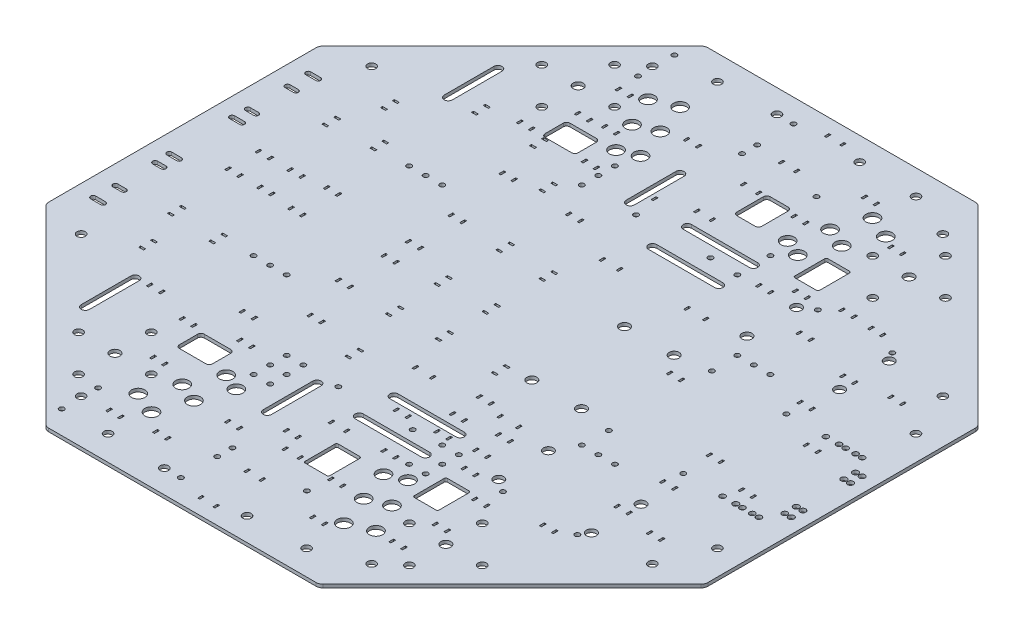
SolidWorks part; units mm, degrees
ref_plane "前视基准面" through (0, 0, 0) normal (0, 0, 1) x (1, 0, 0)
ref_plane "上视基准面" through (0, 0, 0) normal (0, 1, 0) x (1, 0, 0)
ref_plane "右视基准面" through (0, 0, 0) normal (1, 0, 0) x (0, 0, -1)
other "Configuration Table"
ref_plane "基准面1" through (0, 0, 0) normal (0, -1, 0) x (1, 0, 0)
sketch "草图1" plane through (0, 0, 0) normal (0, -1, 0) x (1, 0, 0)
  line L0 (-199.1726, 80.8431) -> (-199.1726, -80.8431)
  line L1 (-198.001, -83.6716) -> (-83.6716, -198.001)
  line L2 (-80.8431, -199.1726) -> (80.8431, -199.1726)
  line L3 (83.6716, -198.001) -> (198.001, -83.6716)
  line L4 (199.1726, -80.8431) -> (199.1726, 80.8431)
  line L5 (198.001, 83.6716) -> (83.6716, 198.001)
  line L6 (80.8431, 199.1726) -> (-80.8431, 199.1726)
  line L7 (-83.6716, 198.001) -> (-198.001, 83.6716)
  line L8 (-182.1726, 63.5) -> (-188.1726, 63.5)
  line L9 (-188.1726, 66.5) -> (-182.1726, 66.5)
  line L10 (-182.1726, 17.5) -> (-188.1726, 17.5)
  line L11 (-188.1726, 20.5) -> (-182.1726, 20.5)
  line L12 (-182.1726, -66.5) -> (-188.1726, -66.5)
  line L13 (-188.1726, -63.5) -> (-182.1726, -63.5)
  line L14 (-182.1726, -20.5) -> (-188.1726, -20.5)
  line L15 (-188.1726, -17.5) -> (-182.1726, -17.5)
  line L16 (-182.6726, 50.5) -> (-187.6726, 50.5)
  line L17 (-187.6726, 53.5) -> (-182.6726, 53.5)
  line L18 (-182.6726, 26.5) -> (-187.6726, 26.5)
  line L19 (-187.6726, 29.5) -> (-182.6726, 29.5)
  line L20 (-182.6726, -53.5) -> (-187.6726, -53.5)
  line L21 (-187.6726, -50.5) -> (-182.6726, -50.5)
  line L22 (-182.6726, -29.5) -> (-187.6726, -29.5)
  line L23 (-187.6726, -26.5) -> (-182.6726, -26.5)
  line L24 (61.2, 58) -> (61.2, 55)
  line L25 (61.2, 55) -> (60, 55)
  line L26 (60, 55) -> (60, 58)
  line L27 (60, 58) -> (61.2, 58)
  line L28 (50, 58) -> (50, 55)
  line L29 (50, 55) -> (48.8, 55)
  line L30 (48.8, 55) -> (48.8, 58)
  line L31 (48.8, 58) -> (50, 58)
  line L32 (-1.2, 58) -> (-1.2, 55)
  line L33 (-1.2, 55) -> (-2.4, 55)
  line L34 (-2.4, 55) -> (-2.4, 58)
  line L35 (-2.4, 58) -> (-1.2, 58)
  line L36 (9.2, 58) -> (9.2, 55)
  line L37 (9.2, 55) -> (8, 55)
  line L38 (8, 55) -> (8, 58)
  line L39 (8, 58) -> (9.2, 58)
  line L40 (61.2, -58) -> (60, -58)
  line L41 (60, -58) -> (60, -55)
  line L42 (60, -55) -> (61.2, -55)
  line L43 (61.2, -55) -> (61.2, -58)
  line L44 (50, -58) -> (48.8, -58)
  line L45 (48.8, -58) -> (48.8, -55)
  line L46 (48.8, -55) -> (50, -55)
  line L47 (50, -55) -> (50, -58)
  line L48 (-1.2, -58) -> (-2.4, -58)
  line L49 (-2.4, -58) -> (-2.4, -55)
  line L50 (-2.4, -55) -> (-1.2, -55)
  line L51 (-1.2, -55) -> (-1.2, -58)
  line L52 (9.2, -58) -> (8, -58)
  line L53 (8, -58) -> (8, -55)
  line L54 (8, -55) -> (9.2, -55)
  line L55 (9.2, -55) -> (9.2, -58)
  line L56 (10, -160) -> (11.2, -160)
  line L57 (11.2, -160) -> (11.2, -163)
  line L58 (11.2, -163) -> (10, -163)
  line L59 (10, -163) -> (10, -160)
  line L60 (0.8, -160) -> (2, -160)
  line L61 (2, -160) -> (2, -163)
  line L62 (2, -163) -> (0.8, -163)
  line L63 (0.8, -163) -> (0.8, -160)
  line L64 (10, -137) -> (11.2, -137)
  line L65 (11.2, -137) -> (11.2, -140)
  line L66 (11.2, -140) -> (10, -140)
  line L67 (10, -140) -> (10, -137)
  line L68 (0.8, -137) -> (2, -137)
  line L69 (2, -137) -> (2, -140)
  line L70 (2, -140) -> (0.8, -140)
  line L71 (0.8, -140) -> (0.8, -137)
  line L72 (10, -109) -> (11.2, -109)
  line L73 (11.2, -109) -> (11.2, -112)
  line L74 (11.2, -112) -> (10, -112)
  line L75 (10, -112) -> (10, -109)
  line L76 (2, -109) -> (2, -112)
  line L77 (2, -112) -> (0.8, -112)
  line L78 (0.8, -112) -> (0.8, -109)
  line L79 (0.8, -109) -> (2, -109)
  line L80 (10, -188) -> (11.2, -188)
  line L81 (11.2, -188) -> (11.2, -190.7495)
  line L82 (11.2, -190.7495) -> (10, -190.7495)
  line L83 (10, -190.7495) -> (10, -188)
  line L84 (2, -188) -> (2, -190.7495)
  line L85 (2, -190.7495) -> (0.8, -190.7495)
  line L86 (0.8, -190.7495) -> (0.8, -188)
  line L87 (0.8, -188) -> (2, -188)
  line L88 (10, 160) -> (10, 163)
  line L89 (10, 163) -> (11.2, 163)
  line L90 (11.2, 163) -> (11.2, 160)
  line L91 (11.2, 160) -> (10, 160)
  line L92 (0.8, 160) -> (0.8, 163)
  line L93 (0.8, 163) -> (2, 163)
  line L94 (2, 163) -> (2, 160)
  line L95 (2, 160) -> (0.8, 160)
  line L96 (10, 137) -> (10, 140)
  line L97 (10, 140) -> (11.2, 140)
  line L98 (11.2, 140) -> (11.2, 137)
  line L99 (11.2, 137) -> (10, 137)
  line L100 (0.8, 137) -> (0.8, 140)
  line L101 (0.8, 140) -> (2, 140)
  line L102 (2, 140) -> (2, 137)
  line L103 (2, 137) -> (0.8, 137)
  line L104 (10, 109) -> (10, 112)
  line L105 (10, 112) -> (11.2, 112)
  line L106 (11.2, 112) -> (11.2, 109)
  line L107 (11.2, 109) -> (10, 109)
  line L108 (2, 109) -> (0.8, 109)
  line L109 (0.8, 109) -> (0.8, 112)
  line L110 (0.8, 112) -> (2, 112)
  line L111 (2, 112) -> (2, 109)
  line L112 (10, 188) -> (10, 190.7495)
  line L113 (10, 190.7495) -> (11.2, 190.7495)
  line L114 (11.2, 190.7495) -> (11.2, 188)
  line L115 (11.2, 188) -> (10, 188)
  line L116 (2, 188) -> (0.8, 188)
  line L117 (0.8, 188) -> (0.8, 190.7495)
  line L118 (0.8, 190.7495) -> (2, 190.7495)
  line L119 (2, 190.7495) -> (2, 188)
  line L120 (-11, 7.2) -> (-8, 7.2)
  line L121 (-8, 7.2) -> (-8, 6)
  line L122 (-8, 6) -> (-11, 6)
  line L123 (-11, 6) -> (-11, 7.2)
  line L124 (-11, 0) -> (-8, 0)
  line L125 (-8, 0) -> (-8, -1.2)
  line L126 (-8, -1.2) -> (-11, -1.2)
  line L127 (-11, -1.2) -> (-11, 0)
  line L128 (-11, 28.4) -> (-8, 28.4)
  line L129 (-8, 28.4) -> (-8, 27.2)
  line L130 (-8, 27.2) -> (-11, 27.2)
  line L131 (-11, 27.2) -> (-11, 28.4)
  line L132 (-8, 35.6) -> (-8, 34.4)
  line L133 (-8, 34.4) -> (-11, 34.4)
  line L134 (-11, 34.4) -> (-11, 35.6)
  line L135 (-11, 35.6) -> (-8, 35.6)
  line L136 (-39, 30.4) -> (-36, 30.4)
  line L137 (-36, 30.4) -> (-36, 29.2)
  line L138 (-36, 29.2) -> (-39, 29.2)
  line L139 (-39, 29.2) -> (-39, 30.4)
  line L140 (-36, 37.6) -> (-36, 36.4)
  line L141 (-36, 36.4) -> (-39, 36.4)
  line L142 (-39, 36.4) -> (-39, 37.6)
  line L143 (-39, 37.6) -> (-36, 37.6)
  line L144 (-40.1232, 0) -> (-37.1232, 0)
  line L145 (-37.1232, 0) -> (-37.1232, -1.2)
  line L146 (-37.1232, -1.2) -> (-40.1232, -1.2)
  line L147 (-40.1232, -1.2) -> (-40.1232, 0)
  line L148 (-37.1232, 7.2) -> (-37.1232, 6)
  line L149 (-37.1232, 6) -> (-40.1232, 6)
  line L150 (-40.1232, 6) -> (-40.1232, 7.2)
  line L151 (-40.1232, 7.2) -> (-37.1232, 7.2)
  line L152 (-64.2, 32.5786) -> (-64.2, 35.5786)
  line L153 (-64.2, 35.5786) -> (-63, 35.5786)
  line L154 (-63, 35.5786) -> (-63, 32.5786)
  line L155 (-63, 32.5786) -> (-64.2, 32.5786)
  line L156 (-71.4, 35.5786) -> (-70.2, 35.5786)
  line L157 (-70.2, 35.5786) -> (-70.2, 32.5786)
  line L158 (-70.2, 32.5786) -> (-71.4, 32.5786)
  line L159 (-71.4, 32.5786) -> (-71.4, 35.5786)
  line L160 (-63.3232, 5.8635) -> (-63.3232, 8.8635)
  line L161 (-63.3232, 8.8635) -> (-62.1232, 8.8635)
  line L162 (-62.1232, 8.8635) -> (-62.1232, 5.8635)
  line L163 (-62.1232, 5.8635) -> (-63.3232, 5.8635)
  line L164 (-70.5232, 8.8635) -> (-69.3232, 8.8635)
  line L165 (-69.3232, 8.8635) -> (-69.3232, 5.8635)
  line L166 (-69.3232, 5.8635) -> (-70.5232, 5.8635)
  line L167 (-70.5232, 5.8635) -> (-70.5232, 8.8635)
  line L168 (-11, -28.4) -> (-11, -27.2)
  line L169 (-11, -27.2) -> (-8, -27.2)
  line L170 (-8, -27.2) -> (-8, -28.4)
  line L171 (-8, -28.4) -> (-11, -28.4)
  line L172 (-8, -35.6) -> (-11, -35.6)
  line L173 (-11, -35.6) -> (-11, -34.4)
  line L174 (-11, -34.4) -> (-8, -34.4)
  line L175 (-8, -34.4) -> (-8, -35.6)
  line L176 (-39, -30.4) -> (-39, -29.2)
  line L177 (-39, -29.2) -> (-36, -29.2)
  line L178 (-36, -29.2) -> (-36, -30.4)
  line L179 (-36, -30.4) -> (-39, -30.4)
  line L180 (-36, -37.6) -> (-39, -37.6)
  line L181 (-39, -37.6) -> (-39, -36.4)
  line L182 (-39, -36.4) -> (-36, -36.4)
  line L183 (-36, -36.4) -> (-36, -37.6)
  line L184 (-64.2, -32.5786) -> (-63, -32.5786)
  line L185 (-63, -32.5786) -> (-63, -35.5786)
  line L186 (-63, -35.5786) -> (-64.2, -35.5786)
  line L187 (-64.2, -35.5786) -> (-64.2, -32.5786)
  line L188 (-71.4, -35.5786) -> (-71.4, -32.5786)
  line L189 (-71.4, -32.5786) -> (-70.2, -32.5786)
  line L190 (-70.2, -32.5786) -> (-70.2, -35.5786)
  line L191 (-70.2, -35.5786) -> (-71.4, -35.5786)
  line L192 (-63.3232, -5.8635) -> (-62.1232, -5.8635)
  line L193 (-62.1232, -5.8635) -> (-62.1232, -8.8635)
  line L194 (-62.1232, -8.8635) -> (-63.3232, -8.8635)
  line L195 (-63.3232, -8.8635) -> (-63.3232, -5.8635)
  line L196 (-70.5232, -8.8635) -> (-70.5232, -5.8635)
  line L197 (-70.5232, -5.8635) -> (-69.3232, -5.8635)
  line L198 (-69.3232, -5.8635) -> (-69.3232, -8.8635)
  line L199 (-69.3232, -8.8635) -> (-70.5232, -8.8635)
  line L200 (138.4, 66.7151) -> (138.4, 69.7151)
  line L201 (138.4, 69.7151) -> (139.6, 69.7151)
  line L202 (139.6, 69.7151) -> (139.6, 66.7151)
  line L203 (139.6, 66.7151) -> (138.4, 66.7151)
  line L204 (131.2, 69.7151) -> (132.4, 69.7151)
  line L205 (132.4, 69.7151) -> (132.4, 66.7151)
  line L206 (132.4, 66.7151) -> (131.2, 66.7151)
  line L207 (131.2, 66.7151) -> (131.2, 69.7151)
  line L208 (139.2768, 40) -> (139.2768, 43)
  line L209 (139.2768, 43) -> (140.4768, 43)
  line L210 (140.4768, 43) -> (140.4768, 40)
  line L211 (140.4768, 40) -> (139.2768, 40)
  line L212 (132.0768, 43) -> (133.2768, 43)
  line L213 (133.2768, 43) -> (133.2768, 40)
  line L214 (133.2768, 40) -> (132.0768, 40)
  line L215 (132.0768, 40) -> (132.0768, 43)
  line L216 (138.4, -66.7151) -> (139.6, -66.7151)
  line L217 (139.6, -66.7151) -> (139.6, -69.7151)
  line L218 (139.6, -69.7151) -> (138.4, -69.7151)
  line L219 (138.4, -69.7151) -> (138.4, -66.7151)
  line L220 (131.2, -69.7151) -> (131.2, -66.7151)
  line L221 (131.2, -66.7151) -> (132.4, -66.7151)
  line L222 (132.4, -66.7151) -> (132.4, -69.7151)
  line L223 (132.4, -69.7151) -> (131.2, -69.7151)
  line L224 (139.2768, -40) -> (140.4768, -40)
  line L225 (140.4768, -40) -> (140.4768, -43)
  line L226 (140.4768, -43) -> (139.2768, -43)
  line L227 (139.2768, -43) -> (139.2768, -40)
  line L228 (132.0768, -43) -> (132.0768, -40)
  line L229 (132.0768, -40) -> (133.2768, -40)
  line L230 (133.2768, -40) -> (133.2768, -43)
  line L231 (133.2768, -43) -> (132.0768, -43)
  line L232 (-29, 64.8) -> (-26, 64.8)
  line L233 (-26, 64.8) -> (-26, 63.6)
  line L234 (-26, 63.6) -> (-29, 63.6)
  line L235 (-29, 63.6) -> (-29, 64.8)
  line L236 (-26, 72) -> (-26, 70.8)
  line L237 (-26, 70.8) -> (-29, 70.8)
  line L238 (-29, 70.8) -> (-29, 72)
  line L239 (-29, 72) -> (-26, 72)
  line L240 (-29.2, -71.6) -> (-29.2, -68.6)
  line L241 (-29.2, -68.6) -> (-28, -68.6)
  line L242 (-28, -68.6) -> (-28, -71.6)
  line L243 (-28, -71.6) -> (-29.2, -71.6)
  line L244 (-36.4, -68.6) -> (-35.2, -68.6)
  line L245 (-35.2, -68.6) -> (-35.2, -71.6)
  line L246 (-35.2, -71.6) -> (-36.4, -71.6)
  line L247 (-36.4, -71.6) -> (-36.4, -68.6)
  line L248 (-57.4, -80.8) -> (-54.4, -80.8)
  line L249 (-54.4, -80.8) -> (-54.4, -82)
  line L250 (-54.4, -82) -> (-57.4, -82)
  line L251 (-57.4, -82) -> (-57.4, -80.8)
  line L252 (-54.4, -73.6) -> (-54.4, -74.8)
  line L253 (-54.4, -74.8) -> (-57.4, -74.8)
  line L254 (-57.4, -74.8) -> (-57.4, -73.6)
  line L255 (-57.4, -73.6) -> (-54.4, -73.6)
  line L256 (-83.4, -101.2) -> (-80.4, -101.2)
  line L257 (-80.4, -101.2) -> (-80.4, -102.4)
  line L258 (-80.4, -102.4) -> (-83.4, -102.4)
  line L259 (-83.4, -102.4) -> (-83.4, -101.2)
  line L260 (-80.4, -94) -> (-80.4, -95.2)
  line L261 (-80.4, -95.2) -> (-83.4, -95.2)
  line L262 (-83.4, -95.2) -> (-83.4, -94)
  line L263 (-83.4, -94) -> (-80.4, -94)
  line L264 (-118.4, -101.0819) -> (-115.4, -101.0819)
  line L265 (-115.4, -101.0819) -> (-115.4, -102.2819)
  line L266 (-115.4, -102.2819) -> (-118.4, -102.2819)
  line L267 (-118.4, -102.2819) -> (-118.4, -101.0819)
  line L268 (-115.4, -93.8819) -> (-115.4, -95.0819)
  line L269 (-115.4, -95.0819) -> (-118.4, -95.0819)
  line L270 (-118.4, -95.0819) -> (-118.4, -93.8819)
  line L271 (-118.4, -93.8819) -> (-115.4, -93.8819)
  line L272 (40.2, 68) -> (40.2, 71)
  line L273 (40.2, 71) -> (41.4, 71)
  line L274 (41.4, 71) -> (41.4, 68)
  line L275 (41.4, 68) -> (40.2, 68)
  line L276 (33, 71) -> (34.2, 71)
  line L277 (34.2, 71) -> (34.2, 68)
  line L278 (34.2, 68) -> (33, 68)
  line L279 (33, 68) -> (33, 71)
  line L280 (39.4, 51) -> (39.4, 54)
  line L281 (39.4, 54) -> (40.6, 54)
  line L282 (40.6, 54) -> (40.6, 51)
  line L283 (40.6, 51) -> (39.4, 51)
  line L284 (32.2, 54) -> (33.4, 54)
  line L285 (33.4, 54) -> (33.4, 51)
  line L286 (33.4, 51) -> (32.2, 51)
  line L287 (32.2, 51) -> (32.2, 54)
  line L288 (23.8401, 29.177) -> (26.8401, 29.177)
  line L289 (26.8401, 29.177) -> (26.8401, 27.977)
  line L290 (26.8401, 27.977) -> (23.8401, 27.977)
  line L291 (23.8401, 27.977) -> (23.8401, 29.177)
  line L292 (26.8401, 36.377) -> (26.8401, 35.177)
  line L293 (26.8401, 35.177) -> (23.8401, 35.177)
  line L294 (23.8401, 35.177) -> (23.8401, 36.377)
  line L295 (23.8401, 36.377) -> (26.8401, 36.377)
  line L296 (-130.4, -51.6819) -> (-127.4, -51.6819)
  line L297 (-127.4, -51.6819) -> (-127.4, -52.8819)
  line L298 (-127.4, -52.8819) -> (-130.4, -52.8819)
  line L299 (-130.4, -52.8819) -> (-130.4, -51.6819)
  line L300 (-127.4, -44.4819) -> (-127.4, -45.6819)
  line L301 (-127.4, -45.6819) -> (-130.4, -45.6819)
  line L302 (-130.4, -45.6819) -> (-130.4, -44.4819)
  line L303 (-130.4, -44.4819) -> (-127.4, -44.4819)
  line L304 (-148.4, -76.0819) -> (-145.4, -76.0819)
  line L305 (-145.4, -76.0819) -> (-145.4, -77.2819)
  line L306 (-145.4, -77.2819) -> (-148.4, -77.2819)
  line L307 (-148.4, -77.2819) -> (-148.4, -76.0819)
  line L308 (-145.4, -68.8819) -> (-145.4, -70.0819)
  line L309 (-145.4, -70.0819) -> (-148.4, -70.0819)
  line L310 (-148.4, -70.0819) -> (-148.4, -68.8819)
  line L311 (-148.4, -68.8819) -> (-145.4, -68.8819)
  line L312 (-157.4, -49.6819) -> (-154.4, -49.6819)
  line L313 (-154.4, -49.6819) -> (-154.4, -50.8819)
  line L314 (-154.4, -50.8819) -> (-157.4, -50.8819)
  line L315 (-157.4, -50.8819) -> (-157.4, -49.6819)
  line L316 (-154.4, -42.4819) -> (-154.4, -43.6819)
  line L317 (-154.4, -43.6819) -> (-157.4, -43.6819)
  line L318 (-157.4, -43.6819) -> (-157.4, -42.4819)
  line L319 (-157.4, -42.4819) -> (-154.4, -42.4819)
  line L320 (-116.2, -12.2659) -> (-116.2, -9.2659)
  line L321 (-116.2, -9.2659) -> (-115, -9.2659)
  line L322 (-115, -9.2659) -> (-115, -12.2659)
  line L323 (-115, -12.2659) -> (-116.2, -12.2659)
  line L324 (-123.4, -9.2659) -> (-122.2, -9.2659)
  line L325 (-122.2, -9.2659) -> (-122.2, -12.2659)
  line L326 (-122.2, -12.2659) -> (-123.4, -12.2659)
  line L327 (-123.4, -12.2659) -> (-123.4, -9.2659)
  line L328 (-136.6, -10.6185) -> (-136.6, -7.6185)
  line L329 (-136.6, -7.6185) -> (-135.4, -7.6185)
  line L330 (-135.4, -7.6185) -> (-135.4, -10.6185)
  line L331 (-135.4, -10.6185) -> (-136.6, -10.6185)
  line L332 (-143.8, -7.6185) -> (-142.6, -7.6185)
  line L333 (-142.6, -7.6185) -> (-142.6, -10.6185)
  line L334 (-142.6, -10.6185) -> (-143.8, -10.6185)
  line L335 (-143.8, -10.6185) -> (-143.8, -7.6185)
  line L336 (-155.8233, -10.6528) -> (-155.8233, -7.6528)
  line L337 (-155.8233, -7.6528) -> (-154.6233, -7.6528)
  line L338 (-154.6233, -7.6528) -> (-154.6233, -10.6528)
  line L339 (-154.6233, -10.6528) -> (-155.8233, -10.6528)
  line L340 (-163.0233, -7.6528) -> (-161.8233, -7.6528)
  line L341 (-161.8233, -7.6528) -> (-161.8233, -10.6528)
  line L342 (-161.8233, -10.6528) -> (-163.0233, -10.6528)
  line L343 (-163.0233, -10.6528) -> (-163.0233, -7.6528)
  line L344 (-130.4, 51.6819) -> (-130.4, 52.8819)
  line L345 (-130.4, 52.8819) -> (-127.4, 52.8819)
  line L346 (-127.4, 52.8819) -> (-127.4, 51.6819)
  line L347 (-127.4, 51.6819) -> (-130.4, 51.6819)
  line L348 (-127.4, 44.4819) -> (-130.4, 44.4819)
  line L349 (-130.4, 44.4819) -> (-130.4, 45.6819)
  line L350 (-130.4, 45.6819) -> (-127.4, 45.6819)
  line L351 (-127.4, 45.6819) -> (-127.4, 44.4819)
  line L352 (-148.4, 76.0819) -> (-148.4, 77.2819)
  line L353 (-148.4, 77.2819) -> (-145.4, 77.2819)
  line L354 (-145.4, 77.2819) -> (-145.4, 76.0819)
  line L355 (-145.4, 76.0819) -> (-148.4, 76.0819)
  line L356 (-145.4, 68.8819) -> (-148.4, 68.8819)
  line L357 (-148.4, 68.8819) -> (-148.4, 70.0819)
  line L358 (-148.4, 70.0819) -> (-145.4, 70.0819)
  line L359 (-145.4, 70.0819) -> (-145.4, 68.8819)
  line L360 (-157.4, 49.6819) -> (-157.4, 50.8819)
  line L361 (-157.4, 50.8819) -> (-154.4, 50.8819)
  line L362 (-154.4, 50.8819) -> (-154.4, 49.6819)
  line L363 (-154.4, 49.6819) -> (-157.4, 49.6819)
  line L364 (-154.4, 42.4819) -> (-157.4, 42.4819)
  line L365 (-157.4, 42.4819) -> (-157.4, 43.6819)
  line L366 (-157.4, 43.6819) -> (-154.4, 43.6819)
  line L367 (-154.4, 43.6819) -> (-154.4, 42.4819)
  line L368 (-116.2, 12.2659) -> (-115, 12.2659)
  line L369 (-115, 12.2659) -> (-115, 9.2659)
  line L370 (-115, 9.2659) -> (-116.2, 9.2659)
  line L371 (-116.2, 9.2659) -> (-116.2, 12.2659)
  line L372 (-123.4, 9.2659) -> (-123.4, 12.2659)
  line L373 (-123.4, 12.2659) -> (-122.2, 12.2659)
  line L374 (-122.2, 12.2659) -> (-122.2, 9.2659)
  line L375 (-122.2, 9.2659) -> (-123.4, 9.2659)
  line L376 (-136.6, 10.6185) -> (-135.4, 10.6185)
  line L377 (-135.4, 10.6185) -> (-135.4, 7.6185)
  line L378 (-135.4, 7.6185) -> (-136.6, 7.6185)
  line L379 (-136.6, 7.6185) -> (-136.6, 10.6185)
  line L380 (-143.8, 7.6185) -> (-143.8, 10.6185)
  line L381 (-143.8, 10.6185) -> (-142.6, 10.6185)
  line L382 (-142.6, 10.6185) -> (-142.6, 7.6185)
  line L383 (-142.6, 7.6185) -> (-143.8, 7.6185)
  line L384 (-155.8233, 10.6528) -> (-154.6233, 10.6528)
  line L385 (-154.6233, 10.6528) -> (-154.6233, 7.6528)
  line L386 (-154.6233, 7.6528) -> (-155.8233, 7.6528)
  line L387 (-155.8233, 7.6528) -> (-155.8233, 10.6528)
  line L388 (-163.0233, 7.6528) -> (-163.0233, 10.6528)
  line L389 (-163.0233, 10.6528) -> (-161.8233, 10.6528)
  line L390 (-161.8233, 10.6528) -> (-161.8233, 7.6528)
  line L391 (-161.8233, 7.6528) -> (-163.0233, 7.6528)
  line L392 (139.3769, 15.0316) -> (140.5769, 15.0316)
  line L393 (140.5769, 15.0316) -> (140.5769, 12.0316)
  line L394 (140.5769, 12.0316) -> (139.3769, 12.0316)
  line L395 (139.3769, 12.0316) -> (139.3769, 15.0316)
  line L396 (132.1769, 12.0316) -> (132.1769, 15.0316)
  line L397 (132.1769, 15.0316) -> (133.3769, 15.0316)
  line L398 (133.3769, 15.0316) -> (133.3769, 12.0316)
  line L399 (133.3769, 12.0316) -> (132.1769, 12.0316)
  line L400 (125.6995, 101.9823) -> (126.8995, 101.9823)
  line L401 (126.8995, 101.9823) -> (126.8995, 98.9823)
  line L402 (126.8995, 98.9823) -> (125.6995, 98.9823)
  line L403 (125.6995, 98.9823) -> (125.6995, 101.9823)
  line L404 (118.4995, 98.9823) -> (118.4995, 101.9823)
  line L405 (118.4995, 101.9823) -> (119.6995, 101.9823)
  line L406 (119.6995, 101.9823) -> (119.6995, 98.9823)
  line L407 (119.6995, 98.9823) -> (118.4995, 98.9823)
  line L408 (121.8695, -100.1551) -> (123.0695, -100.1551)
  line L409 (123.0695, -100.1551) -> (123.0695, -103.1551)
  line L410 (123.0695, -103.1551) -> (121.8695, -103.1551)
  line L411 (121.8695, -103.1551) -> (121.8695, -100.1551)
  line L412 (114.6695, -103.1551) -> (114.6695, -100.1551)
  line L413 (114.6695, -100.1551) -> (115.8695, -100.1551)
  line L414 (115.8695, -100.1551) -> (115.8695, -103.1551)
  line L415 (115.8695, -103.1551) -> (114.6695, -103.1551)
  line L416 (-32.62, -143.2851) -> (-31.42, -143.2851)
  line L417 (-31.42, -143.2851) -> (-31.42, -146.2851)
  line L418 (-31.42, -146.2851) -> (-32.62, -146.2851)
  line L419 (-32.62, -146.2851) -> (-32.62, -143.2851)
  line L420 (-39.82, -146.2851) -> (-39.82, -143.2851)
  line L421 (-39.82, -143.2851) -> (-38.62, -143.2851)
  line L422 (-38.62, -143.2851) -> (-38.62, -146.2851)
  line L423 (-38.62, -146.2851) -> (-39.82, -146.2851)
  line L424 (-18.4576, -102.541) -> (-17.2576, -102.541)
  line L425 (-17.2576, -102.541) -> (-17.2576, -105.541)
  line L426 (-17.2576, -105.541) -> (-18.4576, -105.541)
  line L427 (-18.4576, -105.541) -> (-18.4576, -102.541)
  line L428 (79.5602, -96.8568) -> (80.7602, -96.8568)
  line L429 (80.7602, -96.8568) -> (80.7602, -99.8568)
  line L430 (80.7602, -99.8568) -> (79.5602, -99.8568)
  line L431 (79.5602, -99.8568) -> (79.5602, -96.8568)
  line L432 (72.3602, -99.8568) -> (72.3602, -96.8568)
  line L433 (72.3602, -96.8568) -> (73.5602, -96.8568)
  line L434 (73.5602, -96.8568) -> (73.5602, -99.8568)
  line L435 (73.5602, -99.8568) -> (72.3602, -99.8568)
  line L436 (-62.6219, 96.7032) -> (-61.4219, 96.7032)
  line L437 (-61.4219, 96.7032) -> (-61.4219, 93.7032)
  line L438 (-61.4219, 93.7032) -> (-62.6219, 93.7032)
  line L439 (-62.6219, 93.7032) -> (-62.6219, 96.7032)
  line L440 (-69.8219, 93.7032) -> (-69.8219, 96.7032)
  line L441 (-69.8219, 96.7032) -> (-68.6219, 96.7032)
  line L442 (-68.6219, 96.7032) -> (-68.6219, 93.7032)
  line L443 (-68.6219, 93.7032) -> (-69.8219, 93.7032)
  line L444 (-118.5906, 95.2052) -> (-117.3906, 95.2052)
  line L445 (-117.3906, 95.2052) -> (-117.3906, 92.2052)
  line L446 (-117.3906, 92.2052) -> (-118.5906, 92.2052)
  line L447 (-118.5906, 92.2052) -> (-118.5906, 95.2052)
  line L448 (-125.7906, 92.2052) -> (-125.7906, 95.2052)
  line L449 (-125.7906, 95.2052) -> (-124.5906, 95.2052)
  line L450 (-124.5906, 95.2052) -> (-124.5906, 92.2052)
  line L451 (-124.5906, 92.2052) -> (-125.7906, 92.2052)
  line L452 (-54.3969, 62.4752) -> (-53.1969, 62.4752)
  line L453 (-53.1969, 62.4752) -> (-53.1969, 59.4752)
  line L454 (-53.1969, 59.4752) -> (-54.3969, 59.4752)
  line L455 (-54.3969, 59.4752) -> (-54.3969, 62.4752)
  line L456 (-61.5969, 59.4752) -> (-61.5969, 62.4752)
  line L457 (-61.5969, 62.4752) -> (-60.3969, 62.4752)
  line L458 (-60.3969, 62.4752) -> (-60.3969, 59.4752)
  line L459 (-60.3969, 59.4752) -> (-61.5969, 59.4752)
  line L460 (84.553, -15.8352) -> (85.753, -15.8352)
  line L461 (85.753, -15.8352) -> (85.753, -18.8352)
  line L462 (85.753, -18.8352) -> (84.553, -18.8352)
  line L463 (84.553, -18.8352) -> (84.553, -15.8352)
  line L464 (77.353, -18.8352) -> (77.353, -15.8352)
  line L465 (77.353, -15.8352) -> (78.553, -15.8352)
  line L466 (78.553, -15.8352) -> (78.553, -18.8352)
  line L467 (78.553, -18.8352) -> (77.353, -18.8352)
  line L468 (162.0567, 73.7648) -> (163.2567, 73.7648)
  line L469 (163.2567, 73.7648) -> (163.2567, 70.7648)
  line L470 (163.2567, 70.7648) -> (162.0567, 70.7648)
  line L471 (162.0567, 70.7648) -> (162.0567, 73.7648)
  line L472 (154.8567, 70.7648) -> (154.8567, 73.7648)
  line L473 (154.8567, 73.7648) -> (156.0567, 73.7648)
  line L474 (156.0567, 73.7648) -> (156.0567, 70.7648)
  line L475 (156.0567, 70.7648) -> (154.8567, 70.7648)
  line L476 (163.9292, -70.2421) -> (165.1292, -70.2421)
  line L477 (165.1292, -70.2421) -> (165.1292, -73.2421)
  line L478 (165.1292, -73.2421) -> (163.9292, -73.2421)
  line L479 (163.9292, -73.2421) -> (163.9292, -70.2421)
  line L480 (156.7292, -73.2421) -> (156.7292, -70.2421)
  line L481 (156.7292, -70.2421) -> (157.9292, -70.2421)
  line L482 (157.9292, -70.2421) -> (157.9292, -73.2421)
  line L483 (157.9292, -73.2421) -> (156.7292, -73.2421)
  line L484 (163.4185, -19.5163) -> (164.6185, -19.5163)
  line L485 (164.6185, -19.5163) -> (164.6185, -22.5163)
  line L486 (164.6185, -22.5163) -> (163.4185, -22.5163)
  line L487 (163.4185, -22.5163) -> (163.4185, -19.5163)
  line L488 (156.2185, -22.5163) -> (156.2185, -19.5163)
  line L489 (156.2185, -19.5163) -> (157.4185, -19.5163)
  line L490 (157.4185, -19.5163) -> (157.4185, -22.5163)
  line L491 (157.4185, -22.5163) -> (156.2185, -22.5163)
  line L492 (167.3336, 23.5496) -> (168.5336, 23.5496)
  line L493 (168.5336, 23.5496) -> (168.5336, 20.5496)
  line L494 (168.5336, 20.5496) -> (167.3336, 20.5496)
  line L495 (167.3336, 20.5496) -> (167.3336, 23.5496)
  line L496 (160.1336, 20.5496) -> (160.1336, 23.5496)
  line L497 (160.1336, 23.5496) -> (161.3336, 23.5496)
  line L498 (161.3336, 23.5496) -> (161.3336, 20.5496)
  line L499 (161.3336, 20.5496) -> (160.1336, 20.5496)
  line L500 (66, 125) -> (79, 125)
  line L501 (80, 124) -> (80, 106)
  line L502 (79, 105) -> (66, 105)
  line L503 (65, 106) -> (65, 124)
  line L504 (15, 140) -> (28, 140)
  line L505 (29, 139) -> (29, 121)
  line L506 (28, 120) -> (15, 120)
  line L507 (14, 121) -> (14, 139)
  line L508 (66, -105) -> (79, -105)
  line L509 (80, -106) -> (80, -124)
  line L510 (79, -125) -> (66, -125)
  line L511 (65, -124) -> (65, -106)
  line L512 (-83, 118) -> (-67, 118)
  line L513 (-65, 116) -> (-65, 105)
  line L514 (-67, 103) -> (-83, 103)
  line L515 (-85, 105) -> (-85, 116)
  line L516 (-83, -103) -> (-67, -103)
  line L517 (-65, -105) -> (-65, -116)
  line L518 (-67, -118) -> (-83, -118)
  line L519 (-85, -116) -> (-85, -105)
  line L520 (16, -120) -> (27, -120)
  line L521 (29, -122) -> (29, -138)
  line L522 (27, -140) -> (16, -140)
  line L523 (14, -138) -> (14, -122)
  line L524 (66.2, 68) -> (66.2, 65)
  line L525 (66.2, 65) -> (65, 65)
  line L526 (65, 65) -> (65, 68)
  line L527 (65, 68) -> (66.2, 68)
  line L528 (59, 68) -> (59, 65)
  line L529 (59, 65) -> (57.8, 65)
  line L530 (57.8, 65) -> (57.8, 68)
  line L531 (57.8, 68) -> (59, 68)
  line L532 (67.4, 83) -> (67.4, 80)
  line L533 (67.4, 80) -> (66.2, 80)
  line L534 (66.2, 80) -> (66.2, 83)
  line L535 (66.2, 83) -> (67.4, 83)
  line L536 (60.2, 83) -> (60.2, 80)
  line L537 (60.2, 80) -> (59, 80)
  line L538 (59, 80) -> (59, 83)
  line L539 (59, 83) -> (60.2, 83)
  line L540 (73.4, 96) -> (73.4, 93)
  line L541 (73.4, 93) -> (72.2, 93)
  line L542 (72.2, 93) -> (72.2, 96)
  line L543 (72.2, 96) -> (73.4, 96)
  line L544 (66.2, 96) -> (66.2, 93)
  line L545 (66.2, 93) -> (65, 93)
  line L546 (65, 93) -> (65, 96)
  line L547 (65, 96) -> (66.2, 96)
  line L548 (92.8, 109) -> (92.8, 106)
  line L549 (92.8, 106) -> (91.6, 106)
  line L550 (91.6, 106) -> (91.6, 109)
  line L551 (91.6, 109) -> (92.8, 109)
  line L552 (85.6, 109) -> (85.6, 106)
  line L553 (85.6, 106) -> (84.4, 106)
  line L554 (84.4, 106) -> (84.4, 109)
  line L555 (84.4, 109) -> (85.6, 109)
  line L556 (94, 134) -> (94, 131)
  line L557 (94, 131) -> (92.8, 131)
  line L558 (92.8, 131) -> (92.8, 134)
  line L559 (92.8, 134) -> (94, 134)
  line L560 (86.8, 134) -> (86.8, 131)
  line L561 (86.8, 131) -> (85.6, 131)
  line L562 (85.6, 131) -> (85.6, 134)
  line L563 (85.6, 134) -> (86.8, 134)
  line L564 (22.4, 86) -> (22.4, 83)
  line L565 (22.4, 83) -> (21.2, 83)
  line L566 (21.2, 83) -> (21.2, 86)
  line L567 (21.2, 86) -> (22.4, 86)
  line L568 (15.2, 86) -> (15.2, 83)
  line L569 (15.2, 83) -> (14, 83)
  line L570 (14, 83) -> (14, 86)
  line L571 (14, 86) -> (15.2, 86)
  line L572 (46, 85) -> (46, 82)
  line L573 (46, 82) -> (44.8, 82)
  line L574 (44.8, 82) -> (44.8, 85)
  line L575 (44.8, 85) -> (46, 85)
  line L576 (38.8, 85) -> (38.8, 82)
  line L577 (38.8, 82) -> (37.6, 82)
  line L578 (37.6, 82) -> (37.6, 85)
  line L579 (37.6, 85) -> (38.8, 85)
  line L580 (40, 111) -> (40, 108)
  line L581 (40, 108) -> (38.8, 108)
  line L582 (38.8, 108) -> (38.8, 111)
  line L583 (38.8, 111) -> (40, 111)
  line L584 (32.8, 111) -> (32.8, 108)
  line L585 (32.8, 108) -> (31.6, 108)
  line L586 (31.6, 108) -> (31.6, 111)
  line L587 (31.6, 111) -> (32.8, 111)
  line L588 (38.8, 142) -> (38.8, 139)
  line L589 (38.8, 139) -> (37.6, 139)
  line L590 (37.6, 139) -> (37.6, 142)
  line L591 (37.6, 142) -> (38.8, 142)
  line L592 (31.6, 142) -> (31.6, 139)
  line L593 (31.6, 139) -> (30.4, 139)
  line L594 (30.4, 139) -> (30.4, 142)
  line L595 (30.4, 142) -> (31.6, 142)
  line L596 (-0.0985, 130) -> (-0.0985, 127)
  line L597 (-0.0985, 127) -> (-1.2985, 127)
  line L598 (-1.2985, 127) -> (-1.2985, 130)
  line L599 (-1.2985, 130) -> (-0.0985, 130)
  line L600 (-7.2985, 130) -> (-7.2985, 127)
  line L601 (-7.2985, 127) -> (-8.4985, 127)
  line L602 (-8.4985, 127) -> (-8.4985, 130)
  line L603 (-8.4985, 130) -> (-7.2985, 130)
  line L604 (-22.4985, 143) -> (-22.4985, 140)
  line L605 (-22.4985, 140) -> (-23.6985, 140)
  line L606 (-23.6985, 140) -> (-23.6985, 143)
  line L607 (-23.6985, 143) -> (-22.4985, 143)
  line L608 (-29.6985, 143) -> (-29.6985, 140)
  line L609 (-29.6985, 140) -> (-30.8985, 140)
  line L610 (-30.8985, 140) -> (-30.8985, 143)
  line L611 (-30.8985, 143) -> (-29.6985, 143)
  line L612 (-38.8985, 170) -> (-38.8985, 167)
  line L613 (-38.8985, 167) -> (-40.0985, 167)
  line L614 (-40.0985, 167) -> (-40.0985, 170)
  line L615 (-40.0985, 170) -> (-38.8985, 170)
  line L616 (-46.0985, 170) -> (-46.0985, 167)
  line L617 (-46.0985, 167) -> (-47.2985, 167)
  line L618 (-47.2985, 167) -> (-47.2985, 170)
  line L619 (-47.2985, 170) -> (-46.0985, 170)
  line L620 (-64.2985, 172.9544) -> (-64.2985, 169.9544)
  line L621 (-64.2985, 169.9544) -> (-65.4985, 169.9544)
  line L622 (-65.4985, 169.9544) -> (-65.4985, 172.9544)
  line L623 (-65.4985, 172.9544) -> (-64.2985, 172.9544)
  line L624 (-71.4985, 172.9544) -> (-71.4985, 169.9544)
  line L625 (-71.4985, 169.9544) -> (-72.6985, 169.9544)
  line L626 (-72.6985, 169.9544) -> (-72.6985, 172.9544)
  line L627 (-72.6985, 172.9544) -> (-71.4985, 172.9544)
  line L628 (-78.6985, 131.9544) -> (-78.6985, 128.9544)
  line L629 (-78.6985, 128.9544) -> (-79.8985, 128.9544)
  line L630 (-79.8985, 128.9544) -> (-79.8985, 131.9544)
  line L631 (-79.8985, 131.9544) -> (-78.6985, 131.9544)
  line L632 (-85.8985, 131.9544) -> (-85.8985, 128.9544)
  line L633 (-85.8985, 128.9544) -> (-87.0985, 128.9544)
  line L634 (-87.0985, 128.9544) -> (-87.0985, 131.9544)
  line L635 (-87.0985, 131.9544) -> (-85.8985, 131.9544)
  line L636 (-90.0985, 102.9544) -> (-90.0985, 99.9544)
  line L637 (-90.0985, 99.9544) -> (-91.2985, 99.9544)
  line L638 (-91.2985, 99.9544) -> (-91.2985, 102.9544)
  line L639 (-91.2985, 102.9544) -> (-90.0985, 102.9544)
  line L640 (-97.2985, 102.9544) -> (-97.2985, 99.9544)
  line L641 (-97.2985, 99.9544) -> (-98.4985, 99.9544)
  line L642 (-98.4985, 99.9544) -> (-98.4985, 102.9544)
  line L643 (-98.4985, 102.9544) -> (-97.2985, 102.9544)
  line L644 (-75.6985, 80.9544) -> (-75.6985, 77.9544)
  line L645 (-75.6985, 77.9544) -> (-76.8985, 77.9544)
  line L646 (-76.8985, 77.9544) -> (-76.8985, 80.9544)
  line L647 (-76.8985, 80.9544) -> (-75.6985, 80.9544)
  line L648 (-82.8985, 80.9544) -> (-82.8985, 77.9544)
  line L649 (-82.8985, 77.9544) -> (-84.0985, 77.9544)
  line L650 (-84.0985, 77.9544) -> (-84.0985, 80.9544)
  line L651 (-84.0985, 80.9544) -> (-82.8985, 80.9544)
  line L652 (-78, -124) -> (-78, -127)
  line L653 (-78, -127) -> (-79.2, -127)
  line L654 (-79.2, -127) -> (-79.2, -124)
  line L655 (-79.2, -124) -> (-78, -124)
  line L656 (-85.2, -124) -> (-85.2, -127)
  line L657 (-85.2, -127) -> (-86.4, -127)
  line L658 (-86.4, -127) -> (-86.4, -124)
  line L659 (-86.4, -124) -> (-85.2, -124)
  line L660 (-90.9657, -102) -> (-90.9657, -105)
  line L661 (-90.9657, -105) -> (-92.1657, -105)
  line L662 (-92.1657, -105) -> (-92.1657, -102)
  line L663 (-92.1657, -102) -> (-90.9657, -102)
  line L664 (-98.1657, -102) -> (-98.1657, -105)
  line L665 (-98.1657, -105) -> (-99.3657, -105)
  line L666 (-99.3657, -105) -> (-99.3657, -102)
  line L667 (-99.3657, -102) -> (-98.1657, -102)
  line L668 (-69.5657, -70) -> (-69.5657, -73)
  line L669 (-69.5657, -73) -> (-70.7657, -73)
  line L670 (-70.7657, -73) -> (-70.7657, -70)
  line L671 (-70.7657, -70) -> (-69.5657, -70)
  line L672 (-76.7657, -70) -> (-76.7657, -73)
  line L673 (-76.7657, -73) -> (-77.9657, -73)
  line L674 (-77.9657, -73) -> (-77.9657, -70)
  line L675 (-77.9657, -70) -> (-76.7657, -70)
  line L676 (104.8, -101) -> (104.8, -104)
  line L677 (104.8, -104) -> (103.6, -104)
  line L678 (103.6, -104) -> (103.6, -101)
  line L679 (103.6, -101) -> (104.8, -101)
  line L680 (97.6, -101) -> (97.6, -104)
  line L681 (97.6, -104) -> (96.4, -104)
  line L682 (96.4, -104) -> (96.4, -101)
  line L683 (96.4, -101) -> (97.6, -101)
  line L684 (103.8285, -76) -> (103.8285, -79)
  line L685 (103.8285, -79) -> (102.6285, -79)
  line L686 (102.6285, -79) -> (102.6285, -76)
  line L687 (102.6285, -76) -> (103.8285, -76)
  line L688 (96.6285, -76) -> (96.6285, -79)
  line L689 (96.6285, -79) -> (95.4285, -79)
  line L690 (95.4285, -79) -> (95.4285, -76)
  line L691 (95.4285, -76) -> (96.6285, -76)
  line L692 (66.8676, -88.6924) -> (66.8676, -91.6924)
  line L693 (66.8676, -91.6924) -> (65.6676, -91.6924)
  line L694 (65.6676, -91.6924) -> (65.6676, -88.6924)
  line L695 (65.6676, -88.6924) -> (66.8676, -88.6924)
  line L696 (59.6676, -88.6924) -> (59.6676, -91.6924)
  line L697 (59.6676, -91.6924) -> (58.4676, -91.6924)
  line L698 (58.4676, -91.6924) -> (58.4676, -88.6924)
  line L699 (58.4676, -88.6924) -> (59.6676, -88.6924)
  line L700 (41.2281, -135.5544) -> (41.2281, -138.5544)
  line L701 (41.2281, -138.5544) -> (40.0281, -138.5544)
  line L702 (40.0281, -138.5544) -> (40.0281, -135.5544)
  line L703 (40.0281, -135.5544) -> (41.2281, -135.5544)
  line L704 (34.0281, -135.5544) -> (34.0281, -138.5544)
  line L705 (34.0281, -138.5544) -> (32.8281, -138.5544)
  line L706 (32.8281, -138.5544) -> (32.8281, -135.5544)
  line L707 (32.8281, -135.5544) -> (34.0281, -135.5544)
  line L708 (52.509, -166.8591) -> (52.509, -169.8591)
  line L709 (52.509, -169.8591) -> (51.309, -169.8591)
  line L710 (51.309, -169.8591) -> (51.309, -166.8591)
  line L711 (51.309, -166.8591) -> (52.509, -166.8591)
  line L712 (45.309, -166.8591) -> (45.309, -169.8591)
  line L713 (45.309, -169.8591) -> (44.109, -169.8591)
  line L714 (44.109, -169.8591) -> (44.109, -166.8591)
  line L715 (44.109, -166.8591) -> (45.309, -166.8591)
  line L716 (86.5634, -148.7038) -> (86.5634, -151.7038)
  line L717 (86.5634, -151.7038) -> (85.3634, -151.7038)
  line L718 (85.3634, -151.7038) -> (85.3634, -148.7038)
  line L719 (85.3634, -148.7038) -> (86.5634, -148.7038)
  line L720 (79.3634, -148.7038) -> (79.3634, -151.7038)
  line L721 (79.3634, -151.7038) -> (78.1634, -151.7038)
  line L722 (78.1634, -151.7038) -> (78.1634, -148.7038)
  line L723 (78.1634, -148.7038) -> (79.3634, -148.7038)
  line L724 (-78.3605, -149.0161) -> (-78.3605, -152.0161)
  line L725 (-78.3605, -152.0161) -> (-79.5605, -152.0161)
  line L726 (-79.5605, -152.0161) -> (-79.5605, -149.0161)
  line L727 (-79.5605, -149.0161) -> (-78.3605, -149.0161)
  line L728 (-85.5605, -149.0161) -> (-85.5605, -152.0161)
  line L729 (-85.5605, -152.0161) -> (-86.7605, -152.0161)
  line L730 (-86.7605, -152.0161) -> (-86.7605, -149.0161)
  line L731 (-86.7605, -149.0161) -> (-85.5605, -149.0161)
  line L732 (-50.9477, -101.0945) -> (-50.9477, -104.0945)
  line L733 (-50.9477, -104.0945) -> (-52.1477, -104.0945)
  line L734 (-52.1477, -104.0945) -> (-52.1477, -101.0945)
  line L735 (-52.1477, -101.0945) -> (-50.9477, -101.0945)
  line L736 (-58.1477, -101.0945) -> (-58.1477, -104.0945)
  line L737 (-58.1477, -104.0945) -> (-59.3477, -104.0945)
  line L738 (-59.3477, -104.0945) -> (-59.3477, -101.0945)
  line L739 (-59.3477, -101.0945) -> (-58.1477, -101.0945)
  line L740 (-62.9979, -125.3155) -> (-62.9979, -128.3155)
  line L741 (-62.9979, -128.3155) -> (-64.1979, -128.3155)
  line L742 (-64.1979, -128.3155) -> (-64.1979, -125.3155)
  line L743 (-64.1979, -125.3155) -> (-62.9979, -125.3155)
  line L744 (-70.1979, -125.3155) -> (-70.1979, -128.3155)
  line L745 (-70.1979, -128.3155) -> (-71.3979, -128.3155)
  line L746 (-71.3979, -128.3155) -> (-71.3979, -125.3155)
  line L747 (-71.3979, -125.3155) -> (-70.1979, -125.3155)
  line L748 (53.2479, 167.3814) -> (53.2479, 164.3814)
  line L749 (53.2479, 164.3814) -> (52.0479, 164.3814)
  line L750 (52.0479, 164.3814) -> (52.0479, 167.3814)
  line L751 (52.0479, 167.3814) -> (53.2479, 167.3814)
  line L752 (46.0479, 167.3814) -> (46.0479, 164.3814)
  line L753 (46.0479, 164.3814) -> (44.8479, 164.3814)
  line L754 (44.8479, 164.3814) -> (44.8479, 167.3814)
  line L755 (44.8479, 167.3814) -> (46.0479, 167.3814)
  line L756 (89.8533, 155.9683) -> (89.8533, 152.9683)
  line L757 (89.8533, 152.9683) -> (88.6533, 152.9683)
  line L758 (88.6533, 152.9683) -> (88.6533, 155.9683)
  line L759 (88.6533, 155.9683) -> (89.8533, 155.9683)
  line L760 (82.6533, 155.9683) -> (82.6533, 152.9683)
  line L761 (82.6533, 152.9683) -> (81.4533, 152.9683)
  line L762 (81.4533, 152.9683) -> (81.4533, 155.9683)
  line L763 (81.4533, 155.9683) -> (82.6533, 155.9683)
  line L764 (6.8274, 101.6726) -> (46.8274, 101.6726)
  line L765 (46.8274, 96.6726) -> (6.8274, 96.6726)
  line L766 (46.8274, 75.6726) -> (6.8274, 75.6726)
  line L767 (6.8274, 80.6726) -> (46.8274, 80.6726)
  line L768 (6.8274, -75.6726) -> (46.8274, -75.6726)
  line L769 (46.8274, -80.6726) -> (6.8274, -80.6726)
  line L770 (-20.6726, 124.6726) -> (-20.6726, 94.6726)
  line L771 (-25.6726, 94.6726) -> (-25.6726, 124.6726)
  line L772 (-20.6726, -94.6726) -> (-20.6726, -124.6726)
  line L773 (-25.6726, -124.6726) -> (-25.6726, -94.6726)
  line L774 (-135.6726, 94.6726) -> (-135.6726, 124.6726)
  line L775 (-130.6726, 124.6726) -> (-130.6726, 94.6726)
  line L776 (-135.6726, -124.6726) -> (-135.6726, -94.6726)
  line L777 (-130.6726, -94.6726) -> (-130.6726, -124.6726)
  line L778 (6.8274, -96.6726) -> (46.8274, -96.6726)
  line L779 (46.8274, -101.6726) -> (6.8274, -101.6726)
  arc A0 (-199.1726, -80.8431) -> (-198.001, -83.6716) centre (-195.1726, -80.8431) ccw
  arc A1 (-83.6716, -198.001) -> (-80.8431, -199.1726) centre (-80.8431, -195.1726) ccw
  arc A2 (80.8431, -199.1726) -> (83.6716, -198.001) centre (80.8431, -195.1726) ccw
  arc A3 (198.001, -83.6716) -> (199.1726, -80.8431) centre (195.1726, -80.8431) ccw
  arc A4 (199.1726, 80.8431) -> (198.001, 83.6716) centre (195.1726, 80.8431) ccw
  arc A5 (83.6716, 198.001) -> (80.8431, 199.1726) centre (80.8431, 195.1726) ccw
  arc A6 (-80.8431, 199.1726) -> (-83.6716, 198.001) centre (-80.8431, 195.1726) ccw
  arc A7 (-198.001, 83.6716) -> (-199.1726, 80.8431) centre (-195.1726, 80.8431) ccw
  circle A8 centre (-60, 184.1726) radius 2.5
  circle A9 centre (60, 184.1726) radius 2.5
  circle A10 centre (-60, -184.1726) radius 2.5
  circle A11 centre (60, -184.1726) radius 2.5
  circle A12 centre (184.1726, -60) radius 2.5
  circle A13 centre (184.1726, 60) radius 2.5
  circle A14 centre (-87.8033, 172.6561) radius 2.5
  circle A15 centre (-172.6561, 87.8033) radius 2.5
  circle A16 centre (172.6561, -87.8033) radius 2.5
  circle A17 centre (87.8033, -172.6561) radius 2.5
  circle A18 centre (-172.6561, -87.8033) radius 2.5
  circle A19 centre (-87.8033, -172.6561) radius 2.5
  circle A20 centre (87.8033, 172.6561) radius 2.5
  circle A21 centre (172.6561, 87.8033) radius 2.5
  circle A22 centre (47, 89.1726) radius 1.5
  circle A23 centre (47, 109.1726) radius 1.5
  circle A24 centre (-47, 99.1726) radius 1.5
  circle A25 centre (-47, 89.1726) radius 1.5
  circle A26 centre (-47, 109.1726) radius 1.5
  circle A27 centre (99.1726, 47) radius 1.5
  circle A28 centre (89.1726, 47) radius 1.5
  circle A29 centre (109.1726, 47) radius 1.5
  circle A30 centre (99.1726, -47) radius 1.5
  circle A31 centre (89.1726, -47) radius 1.5
  circle A32 centre (109.1726, -47) radius 1.5
  circle A33 centre (-99.1726, 47) radius 1.5
  circle A34 centre (-89.1726, 47) radius 1.5
  circle A35 centre (-109.1726, 47) radius 1.5
  circle A36 centre (-99.1726, -47) radius 1.5
  circle A37 centre (-89.1726, -47) radius 1.5
  circle A38 centre (-109.1726, -47) radius 1.5
  circle A39 centre (47, -89.1726) radius 1.5
  circle A40 centre (47, -109.1726) radius 1.5
  circle A41 centre (-47, -99.1726) radius 1.5
  circle A42 centre (-47, -89.1726) radius 1.5
  circle A43 centre (-47, -109.1726) radius 1.5
  circle A44 centre (57, 89.1726) radius 1.5
  circle A45 centre (57, 99.1726) radius 1.5
  circle A46 centre (57, 109.1726) radius 1.5
  circle A47 centre (-37, 89.1726) radius 1.5
  circle A48 centre (-37, 99.1726) radius 1.5
  circle A49 centre (-37, 109.1726) radius 1.5
  circle A50 centre (180.4726, -31.2) radius 1.65
  circle A51 centre (170.4726, -31.2) radius 1.65
  circle A52 centre (180.4726, 31.2) radius 1.65
  circle A53 centre (170.4726, 31.2) radius 1.65
  circle A54 centre (190.2326, -14.4) radius 1.75
  circle A55 centre (190.2326, -21.4) radius 1.75
  circle A56 centre (190.2326, 14.4) radius 1.75
  circle A57 centre (190.2326, 21.4) radius 1.75
  circle A58 centre (-78, -140) radius 2.5
  circle A59 centre (-100, -162) radius 2.5
  circle A60 centre (-78, 140) radius 2.5
  circle A61 centre (-100, 162) radius 2.5
  circle A62 centre (-100, 118) radius 2.5
  circle A63 centre (100, 162) radius 2.5
  circle A64 centre (100, 118) radius 2.5
  circle A65 centre (100, -162) radius 2.5
  circle A66 centre (100, -118) radius 2.5
  circle A67 centre (-100, -118) radius 2.5
  circle A68 centre (-122, -140) radius 2.5
  circle A69 centre (-122, 140) radius 2.5
  circle A70 centre (78, 140) radius 2.5
  circle A71 centre (122, 140) radius 2.5
  circle A72 centre (78, -140) radius 2.5
  circle A73 centre (122, -140) radius 2.5
  arc A74 (-188.1726, 63.5) -> (-188.1726, 66.5) centre (-188.1726, 65) cw
  arc A75 (-182.1726, 66.5) -> (-182.1726, 63.5) centre (-182.1726, 65) cw
  arc A76 (-182.1726, 20.5) -> (-182.1726, 17.5) centre (-182.1726, 19) cw
  arc A77 (-188.1726, 17.5) -> (-188.1726, 20.5) centre (-188.1726, 19) cw
  arc A78 (-182.1726, -63.5) -> (-182.1726, -66.5) centre (-182.1726, -65) cw
  arc A79 (-188.1726, -66.5) -> (-188.1726, -63.5) centre (-188.1726, -65) cw
  arc A80 (-188.1726, -20.5) -> (-188.1726, -17.5) centre (-188.1726, -19) cw
  arc A81 (-182.1726, -17.5) -> (-182.1726, -20.5) centre (-182.1726, -19) cw
  arc A82 (-187.6726, 50.5) -> (-187.6726, 53.5) centre (-187.6726, 52) cw
  arc A83 (-182.6726, 53.5) -> (-182.6726, 50.5) centre (-182.6726, 52) cw
  arc A84 (-182.6726, 29.5) -> (-182.6726, 26.5) centre (-182.6726, 28) cw
  arc A85 (-187.6726, 26.5) -> (-187.6726, 29.5) centre (-187.6726, 28) cw
  arc A86 (-182.6726, -50.5) -> (-182.6726, -53.5) centre (-182.6726, -52) cw
  arc A87 (-187.6726, -53.5) -> (-187.6726, -50.5) centre (-187.6726, -52) cw
  arc A88 (-187.6726, -29.5) -> (-187.6726, -26.5) centre (-187.6726, -28) cw
  arc A89 (-182.6726, -26.5) -> (-182.6726, -29.5) centre (-182.6726, -28) cw
  circle A90 centre (-25, -185.1726) radius 2.5
  circle A91 centre (25, -185.1726) radius 2.5
  circle A92 centre (25, 185.1726) radius 2.5
  circle A93 centre (-25, 185.1726) radius 2.5
  circle A94 centre (-71.8451, -154.0723) radius 4
  circle A95 centre (-63.3927, -135.9462) radius 4
  circle A96 centre (-63.3927, 135.9462) radius 4
  circle A97 centre (-71.8451, 154.0723) radius 4
  circle A98 centre (63.3927, 135.9462) radius 4
  circle A99 centre (71.8451, 154.0723) radius 4
  circle A100 centre (71.8451, -154.0723) radius 4
  circle A101 centre (63.3927, -135.9462) radius 4
  circle A102 centre (-58.1434, -159.7477) radius 4
  circle A103 centre (58.1434, 159.7477) radius 4
  circle A104 centre (51.303, 140.9539) radius 4
  circle A105 centre (-58.1434, 159.7477) radius 4
  circle A106 centre (58.1434, -159.7477) radius 4
  circle A107 centre (51.303, -140.9539) radius 4
  circle A108 centre (-51.303, -140.9539) radius 4
  circle A109 centre (-51.303, 140.9539) radius 4
  circle A110 centre (54.9404, -117.82) radius 4
  circle A111 centre (44.4626, -122.16) radius 4
  circle A112 centre (-44.4626, -122.16) radius 4
  circle A113 centre (-54.9404, -117.82) radius 4
  circle A114 centre (-54.9404, 117.82) radius 4
  circle A115 centre (-44.4626, 122.16) radius 4
  circle A116 centre (44.4626, 122.16) radius 4
  circle A117 centre (54.9404, 117.82) radius 4
  circle A118 centre (40, 28) radius 3
  circle A119 centre (70, 28) radius 3
  circle A120 centre (40, -28) radius 3
  circle A121 centre (70, -28) radius 3
  circle A122 centre (30, 154) radius 1.5
  circle A123 centre (30, 90) radius 1.5
  circle A124 centre (-15, 90) radius 1.5
  circle A125 centre (-15, 154) radius 1.5
  circle A126 centre (30, -154) radius 1.5
  circle A127 centre (30, -90) radius 1.5
  circle A128 centre (-15, -90) radius 1.5
  circle A129 centre (-15, -154) radius 1.5
  circle A130 centre (186.2326, -21.4) radius 1.75
  circle A131 centre (186.2326, -14.4) radius 1.75
  circle A132 centre (186.2326, 14.4) radius 1.75
  circle A133 centre (186.2326, 21.4) radius 1.65
  circle A134 centre (176.4726, -31.2) radius 1.65
  circle A135 centre (176.4726, 31.2) radius 1.65
  circle A136 centre (166.4726, -31.2) radius 1.65
  circle A137 centre (166.4726, 31.2) radius 1.75
  circle A138 centre (-100, -140) radius 3
  circle A139 centre (-100, 140) radius 3
  circle A140 centre (100, 140) radius 3
  circle A141 centre (100, -140) radius 3
  circle A142 centre (138, 90) radius 3
  circle A143 centre (82, 90) radius 3
  circle A144 centre (138, 60) radius 3
  circle A145 centre (82, 60) radius 3
  circle A146 centre (138, -90) radius 3
  circle A147 centre (82, -90) radius 3
  circle A148 centre (138, -60) radius 3
  circle A149 centre (82, -60) radius 3
  arc A150 (65, 124) -> (66, 125) centre (66, 124) cw
  arc A151 (79, 125) -> (80, 124) centre (79, 124) cw
  arc A152 (80, 106) -> (79, 105) centre (79, 106) cw
  arc A153 (66, 105) -> (65, 106) centre (66, 106) cw
  arc A154 (14, 139) -> (15, 140) centre (15, 139) cw
  arc A155 (28, 140) -> (29, 139) centre (28, 139) cw
  arc A156 (29, 121) -> (28, 120) centre (28, 121) cw
  arc A157 (15, 120) -> (14, 121) centre (15, 121) cw
  arc A158 (65, -106) -> (66, -105) centre (66, -106) cw
  arc A159 (79, -105) -> (80, -106) centre (79, -106) cw
  arc A160 (80, -124) -> (79, -125) centre (79, -124) cw
  arc A161 (66, -125) -> (65, -124) centre (66, -124) cw
  circle A162 centre (-87, 185.1726) radius 1.5
  circle A163 centre (-15, 185.1726) radius 1.5
  circle A164 centre (-87, 163.1726) radius 1.5
  circle A165 centre (-15, 163.1726) radius 1.5
  circle A166 centre (-87, -185.1726) radius 1.5
  circle A167 centre (-15, -185.1726) radius 1.5
  circle A168 centre (-87, -163.1726) radius 1.5
  circle A169 centre (-15, -163.1726) radius 1.5
  arc A170 (-85, 116) -> (-83, 118) centre (-83, 116) cw
  arc A171 (-67, 118) -> (-65, 116) centre (-67, 116) cw
  arc A172 (-65, 105) -> (-67, 103) centre (-67, 105) cw
  arc A173 (-83, 103) -> (-85, 105) centre (-83, 105) cw
  arc A174 (-85, -105) -> (-83, -103) centre (-83, -105) cw
  arc A175 (-67, -103) -> (-65, -105) centre (-67, -105) cw
  arc A176 (-65, -116) -> (-67, -118) centre (-67, -116) cw
  arc A177 (-83, -118) -> (-85, -116) centre (-83, -116) cw
  arc A178 (14, -122) -> (16, -120) centre (16, -122) cw
  arc A179 (27, -120) -> (29, -122) centre (27, -122) cw
  arc A180 (29, -138) -> (27, -140) centre (27, -138) cw
  arc A181 (16, -140) -> (14, -138) centre (16, -138) cw
  circle A182 centre (134.6726, 95.1726) radius 1.5
  circle A183 centre (134.6726, 31.1726) radius 1.5
  circle A184 centre (89.6726, 95.1726) radius 1.5
  circle A185 centre (89.6726, 31.1726) radius 1.5
  circle A186 centre (134.6726, -95.1726) radius 1.5
  circle A187 centre (134.6726, -31.1726) radius 1.5
  circle A188 centre (89.6726, -95.1726) radius 1.5
  circle A189 centre (89.6726, -31.1726) radius 1.5
  arc A190 (6.8274, 96.6726) -> (6.8274, 101.6726) centre (6.8274, 99.1726) cw
  arc A191 (46.8274, 101.6726) -> (46.8274, 96.6726) centre (46.8274, 99.1726) cw
  arc A192 (46.8274, 80.6726) -> (46.8274, 75.6726) centre (46.8274, 78.1726) cw
  arc A193 (6.8274, 75.6726) -> (6.8274, 80.6726) centre (6.8274, 78.1726) cw
  arc A194 (6.8274, -80.6726) -> (6.8274, -75.6726) centre (6.8274, -78.1726) cw
  arc A195 (46.8274, -75.6726) -> (46.8274, -80.6726) centre (46.8274, -78.1726) cw
  arc A196 (-25.6726, 124.6726) -> (-20.6726, 124.6726) centre (-23.1726, 124.6726) cw
  arc A197 (-20.6726, 94.6726) -> (-25.6726, 94.6726) centre (-23.1726, 94.6726) cw
  arc A198 (-25.6726, -94.6726) -> (-20.6726, -94.6726) centre (-23.1726, -94.6726) cw
  arc A199 (-20.6726, -124.6726) -> (-25.6726, -124.6726) centre (-23.1726, -124.6726) cw
  arc A200 (-130.6726, 94.6726) -> (-135.6726, 94.6726) centre (-133.1726, 94.6726) cw
  arc A201 (-135.6726, 124.6726) -> (-130.6726, 124.6726) centre (-133.1726, 124.6726) cw
  arc A202 (-130.6726, -124.6726) -> (-135.6726, -124.6726) centre (-133.1726, -124.6726) cw
  arc A203 (-135.6726, -94.6726) -> (-130.6726, -94.6726) centre (-133.1726, -94.6726) cw
  arc A204 (6.8274, -101.6726) -> (6.8274, -96.6726) centre (6.8274, -99.1726) cw
  arc A205 (46.8274, -96.6726) -> (46.8274, -101.6726) centre (46.8274, -99.1726) cw
extrude "凸台-拉伸1" add sketch "草图1" against normal blind 2
sketch "草图4" plane through (0, 0, 0) normal (0, -1, 0) x (1, 0, 0)
  circle A0 centre (158.4726, 31.2) radius 1.65
  circle A1 centre (158.4726, -31.2) radius 1.65
  circle A2 centre (166.4726, 31.2) radius 1.75 construction
  circle A3 centre (166.4726, -31.2) radius 1.65 construction
  dimension "D1" = 8
  dimension "D2" = 8
  dimension "D3" = 3.3
  dimension "D4" = 3.3
extrude "切除-拉伸1" cut sketch "草图4" against normal up to next
